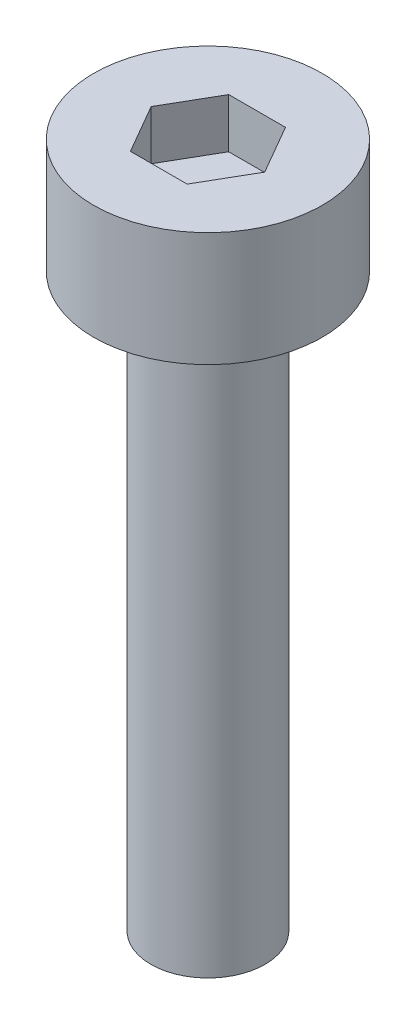
SolidWorks part; units mm, degrees
ref_plane "Front Plane" through (0, 0, 0) normal (0, 0, 1) x (1, 0, 0)
ref_plane "Top Plane" through (0, 0, 0) normal (0, 1, 0) x (1, 0, 0)
ref_plane "Right Plane" through (0, 0, 0) normal (1, 0, 0) x (0, 0, -1)
sketch "Sketch1" plane through (0, 0, 0) normal (0, 1, 0) x (1, 0, 0)
  circle A0 centre (0, 0) radius 1.5
  dimension "D1" = 3
extrude "ScrewShaft" add sketch "Sketch1" along normal blind 15
sketch "Sketch2" plane through (0, 15, 0) normal (0, 1, 0) x (1, 0, 0)
  circle A0 centre (0, 0) radius 3
  dimension "D1" = 6
extrude "Boss-Extrude2" add sketch "Sketch2" along normal blind 3
sketch "Sketch3" plane through (0, 18, 0) normal (0, 1, 0) x (1, 0, 0)
  line L0 (0, 0) -> (0, 1.29) construction
  line L1 (1.4896, 0) -> (0.7448, 1.29)
  line L2 (0.7448, 1.29) -> (-0.7448, 1.29)
  line L3 (-0.7448, 1.29) -> (-1.4896, 0)
  line L4 (-1.4896, 0) -> (-0.7448, -1.29)
  line L5 (-0.7448, -1.29) -> (0.7448, -1.29)
  line L6 (0.7448, -1.29) -> (1.4896, 0)
  circle A0 centre (0, 0) radius 1.29 construction
  dimension "D1" = 2.58
extrude "Cut-Extrude1" cut sketch "Sketch3" against normal blind 1.3
equation "\"X-ROD-SPACING\"=45"
equation "\"Y-ROD-SPACING\"=75"
equation "\"Z-ROD-SPACING\"=17.5"
equation "\"Y-BED-OFFSET\"=2"
equation "\"Y-BED-ROD-INSET\"=3.5"
equation "\"T-SLOT-NUT-FILLET-RADIUS\"=0.25"
equation "\"T-SLOT-SCREW-SHAFT-RADIUS\"=1.75"
equation "\"T-SLOT-SCREW-SHAFT-CUTOUT-LENGTH\"=10.5"
equation "\"T-SLOT-NUT-DEPTH\"=4.2"
equation "\"T-SLOT-NUT-WIDTH\"=3"
equation "\"T-SLOT-NUT-END-DISTANCE\"=8"
equation "\"ACRYLIC-THICKNESS\"=10"
equation "\"ACRYLIC-THICKNESS2\"=4.5"
equation "\"ACRYLIC-TAB-CUTOUT-SIZE\"=\"ACRYLIC-THICKNESS\"+\"ACRYLIC-TAB-TOLERANCE\"*2"
equation "\"ACRYLIC-TAB-WIDTH\"=\"ACRYLIC-THICKNESS\""
equation "\"ACRYLIC-M3-HOLE\"=3.2"
equation "\"SMOOTHROD-CAP-SCREW-DISTANCE\"=20"
equation "\"FRAME-WIDTH-INNER\"=370"
equation "\"NEMA17-HOLE-SPACING\"=31"
equation "\"NEMA17-CENTRAL-CUTOUT\"=22.5"
equation "\"Z-BRACKET-REACH\"=55"
equation "\"TOP-BRACKET-SPACING\"=40"
equation "\"SMOOTHROD-X-LENGTH\"=350"
equation "\"SMOOTHROD-Y-LENGTH\"=350"
equation "\"SMOOTHROD-Z-LENGTH\"=350"
equation "\"SMOOTHROD-TIGHTENING-HEADROOM\"=1"
equation "\"LEADSCREW-Z-LENGTH\"=300"
equation "\"SCREW-LENGTH-FRAME\"=\"ACRYLIC-THICKNESS\" + 10"
equation "\"SCREW-HEAD-RADIUS\"=6"
equation "\"PRINTED-X-SMOOTHROD-DIAMETER\"=8.2"
equation "\"PRINTED-X-SMOOTHROD-CUTOUT\"=10"
equation "\"PRINTED-X-BASE-HEIGHT\"=10"
equation "\"PRINTED-LM8UU-CUTOUT-SIZE\"=16"
equation "\"PRINTED-LM8UU-CUTOUT-LENGTH\"=24.5"
equation "\"PRINTED-X-IDLER-HEIGHT\"=16"
equation "\"PSU-MOUNTING-WIDTH\"=95"
equation "\"PSU-MOUNTING-HEIGHT\"=177"
equation "\"D1@ScrewShaft\"=\"SCREW-LENGTH-MOTOR\""
equation "\"D1@Sketch2\"=\"SCREW-HEAD-RADIUS\""
equation "\"Y-BED-SCREW-SPACING\"=209"
equation "\"Y-BED-SCREW-CUTOUT-SLOT-HEIGHT\"=1"
equation "\"Z-ROD-INSET\"=16"
equation "\"SCREW-LENGTH-MOTOR\"=\"ACRYLIC-THICKNESS\" + 5"
equation "\"Y-BELT-TO-ROD-DISTANCE\"=20"
equation "\"SPOOL-HOLDER-ROD-SPACING\"=150"
